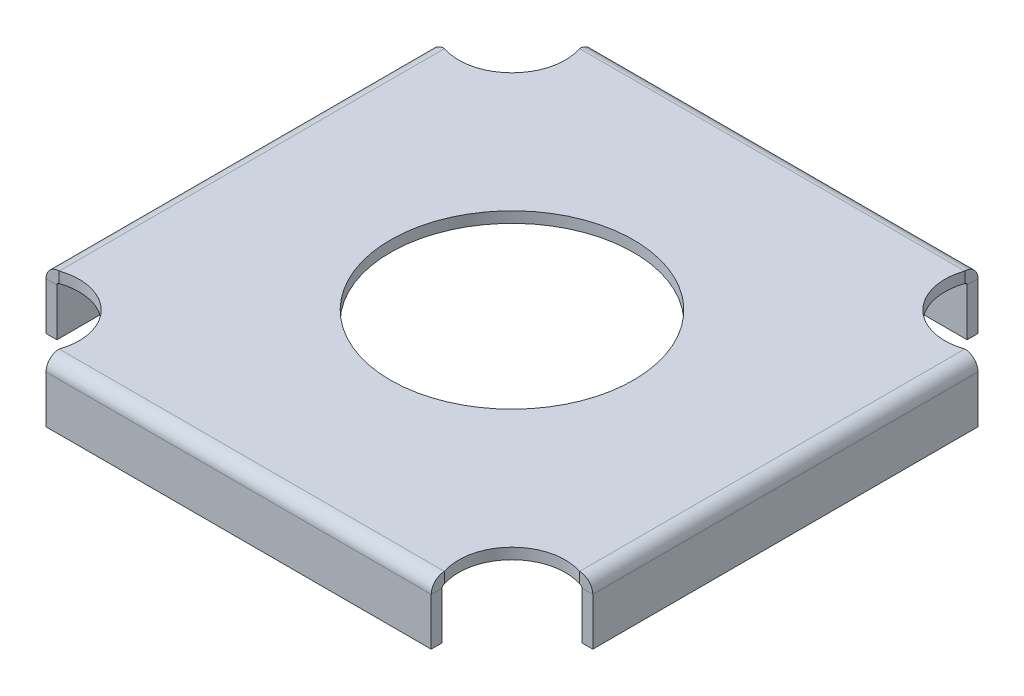
SolidWorks part; units mm, degrees
note: The reader was unsure of these and kept them because the rebuilt part matched: flange length of "Edge-Flange1".
material "Plain Carbon Steel"
ref_plane "Front Plane" through (0, 0, 0) normal (0, 0, 1) x (1, 0, 0)
ref_plane "Top Plane" through (0, 0, 0) normal (0, 1, 0) x (1, 0, 0)
ref_plane "Right Plane" through (0, 0, 0) normal (1, 0, 0) x (0, 0, -1)
sketch "Sketch3" plane through (0, 0, 0) normal (0, 1, 0) x (1, 0, 0)
  line L0 (-60.3828, 81.5594) -> (60.3828, 81.5594)
  line L5 (81.5594, 60.3828) -> (81.5594, -60.3828)
  line L6 (60.3828, -81.5594) -> (-60.3828, -81.5594)
  line L7 (-81.5594, -60.3828) -> (-81.5594, 60.3828)
  line L8 (0, 81.5594) -> (0, -81.5594) construction
  line L9 (-81.5594, 0) -> (81.5594, 0) construction
  line L10 (-76.2, 76.2) -> (-76.2, -76.2) construction
  line L11 (-76.2, -76.2) -> (76.2, -76.2) construction
  line L12 (76.2, -76.2) -> (76.2, 76.2) construction
  line L13 (76.2, 76.2) -> (-76.2, 76.2) construction
  line L14 (-76.2, 76.2) -> (76.2, -76.2) construction
  line L15 (-76.2, -76.2) -> (76.2, 76.2) construction
  arc A0 (60.3828, 81.5594) -> (81.5594, 60.3828) centre (76.2, 76.2) ccw
  arc A1 (-81.5594, 60.3828) -> (-60.3828, 81.5594) centre (-76.2, 76.2) ccw
  arc A2 (-60.3828, -81.5594) -> (-81.5594, -60.3828) centre (-76.2, -76.2) ccw
  arc A3 (81.5594, -60.3828) -> (60.3828, -81.5594) centre (76.2, -76.2) ccw
  circle A4 centre (0, 0) radius 38.1
  dimension "D2" = 163.1188
  dimension "D3" = 152.4
  dimension "D1" = 16.7005
  dimension "D4" = 76.2
base flange "Base-Flange1" sketch "Sketch3" thickness 3.4163 reverse thickness direction no parameters "D1"=0.7366
edge flange "Edge-Flange1" sketch "Sketch16" flange profiles "Sketch16", "Sketch17", "Sketch18", "Sketch19" flange angle 90 flange length 19.05 flange position bend outside bend radius 0.7366 thickness 3.4163 parameters "D6"=10, "D8"=0.254
sketch "Sketch16" plane through (0, -3.4163, 81.5594) normal (0, 0, -1) x (1, 0, 0)
  line L2 (-60.3828, 0) -> (-60.3828, 15.6337)
  line L3 (-60.3828, 15.6337) -> (60.3828, 15.6337)
  line L4 (60.3828, 15.6337) -> (60.3828, 0)
  line L9 (60.3828, 0) -> (-60.3828, 0) construction
  line L10 (60.3828, 0) -> (-60.3828, 0)
sketch "Sketch17" plane through (81.5594, -3.4163, 0) normal (-1, 0, 0) x (0, 0, -1)
  line L0 (60.3828, 0) -> (-60.3828, 0) construction
  line L1 (60.3828, 0) -> (-60.3828, 0)
  line L2 (60.3828, 0) -> (60.3828, 15.6337)
  line L3 (60.3828, 15.6337) -> (-60.3828, 15.6337)
  line L4 (-60.3828, 15.6337) -> (-60.3828, 0)
sketch "Sketch18" plane through (0, -3.4163, -81.5594) normal (0, 0, 1) x (-1, 0, 0)
  line L0 (60.3828, 0) -> (-60.3828, 0) construction
  line L1 (60.3828, 0) -> (-60.3828, 0)
  line L2 (60.3828, 0) -> (60.3828, 15.6337)
  line L3 (60.3828, 15.6337) -> (-60.3828, 15.6337)
  line L4 (-60.3828, 15.6337) -> (-60.3828, 0)
sketch "Sketch19" plane through (-81.5594, -3.4163, 0) normal (1, 0, 0) x (0, 0, 1)
  line L0 (60.3828, 0) -> (-60.3828, 0) construction
  line L1 (60.3828, 0) -> (-60.3828, 0)
  line L2 (60.3828, 0) -> (60.3828, 15.6337)
  line L3 (60.3828, 15.6337) -> (-60.3828, 15.6337)
  line L4 (-60.3828, 15.6337) -> (-60.3828, 0)
bend "EdgeBend1" bend radius 0.7366 bend angle 90 parameters "D5"=1
bend "EdgeBend2" bend radius 0.7366 bend angle 90 parameters "D5"=2
bend "EdgeBend3" bend radius 0.7366 bend angle 90 parameters "D5"=3
bend "EdgeBend4" bend radius 0.7366 bend angle 90 parameters "D5"=4
sketch "Bend-Lines1" [suppressed] plane through (0, 0, 0) normal (0, 1, 0) x (1, 0, 0)
sketch "Bounding-Box1" [suppressed] plane through (0, 0, 0) normal (0, 1, 0) x (1, 0, 0)
sketch "Sketch21" [suppressed] plane through (0, 0, 0) normal (0, 1, 0) x (1, 0, 0)
  line L0 (-83.4795, 54.5408) -> (-83.4795, 46.1588)
  line L1 (-83.4795, 60.3828) -> (-83.4795, -60.3828) construction
  line L2 (-100.2967, 60.3828) -> (-81.5594, 60.3828) construction
  line L3 (-83.4795, 37.7575) -> (-83.4795, 29.3755)
  line L4 (-83.4795, 20.9743) -> (-83.4795, 12.5923)
  line L5 (-83.4795, 4.191) -> (-83.4795, -4.191)
  line L6 (-83.4795, -12.5923) -> (-83.4795, -20.9743)
  line L7 (-83.4795, -29.3755) -> (-83.4795, -37.7575)
  line L8 (-83.4795, -46.1588) -> (-83.4795, -54.5408)
  line L9 (-81.5594, -60.3828) -> (-100.2967, -60.3828) construction
  line L10 (54.5408, 83.4795) -> (46.1588, 83.4795)
  line L11 (37.7575, 83.4795) -> (29.3755, 83.4795)
  line L12 (-46.1588, 83.4795) -> (-54.5408, 83.4795)
  line L13 (-29.3755, 83.4795) -> (-37.7575, 83.4795)
  line L14 (-12.5923, 83.4795) -> (-20.9743, 83.4795)
  line L15 (4.191, 83.4795) -> (-4.191, 83.4795)
  line L16 (20.9743, 83.4795) -> (12.5923, 83.4795)
  line L17 (83.4795, -54.5408) -> (83.4795, -46.1588)
  line L18 (83.4795, -37.7575) -> (83.4795, -29.3755)
  line L19 (83.4795, 46.1588) -> (83.4795, 54.5408)
  line L20 (83.4795, 29.3755) -> (83.4795, 37.7575)
  line L21 (83.4795, 12.5923) -> (83.4795, 20.9743)
  line L22 (83.4795, -4.191) -> (83.4795, 4.191)
  line L23 (83.4795, -20.9743) -> (83.4795, -12.5923)
  line L24 (-54.5408, -83.4795) -> (-46.1588, -83.4795)
  line L25 (-37.7575, -83.4795) -> (-29.3755, -83.4795)
  line L26 (46.1588, -83.4795) -> (54.5408, -83.4795)
  line L27 (29.3755, -83.4795) -> (37.7575, -83.4795)
  line L28 (12.5923, -83.4795) -> (20.9743, -83.4795)
  line L29 (-4.191, -83.4795) -> (4.191, -83.4795)
  line L30 (-20.9743, -83.4795) -> (-12.5923, -83.4795)
  line L31 (60.3828, 83.4795) -> (-60.3828, 83.4795) construction
  line L32 (83.4795, -60.3828) -> (83.4795, 60.3828) construction
  point P65 (0, 0)
  dimension "D1" = 5.842
  dimension "D2" = 8.382
  dimension "D4" = 5.842
  dimension "D3" = 7
  dimension "D5" = 4
extrude "Cut-Extrude-Thin1" [suppressed] cut sketch "Sketch21" against normal through all thin
sheet metal parameters "Sheet-Metal1" thickness 3.4163 parameters "D1"=0.7366
flat pattern "Flat-Pattern1" [suppressed]
sketch "Bend-Lines2" plane through (0, 0, 0) normal (0, 1, 0) x (1, 0, 0)
sketch3d "Bounding-Box2" [suppressed]
  line L0 (2.1844, -2.1844, 0) -> (-154.5844, -2.1844, 0) construction
  line L1 (2.1844, 154.5844, 0) -> (-154.5844, 154.5844, 0) construction
  line L2 (2.1844, -2.1844, 0) -> (2.1844, 154.5844, 0) construction
  line L3 (-154.5844, -2.1844, 0) -> (-154.5844, 154.5844, 0) construction
sheet metal parameters "Sheet-Metal2" thickness 3.4163 parameters "D1"=0.7366
flat pattern "Flat-Pattern1"
sketch "Bend-Lines2" plane through (0, 0, 0) normal (0, 1, 0) x (1, 0, 0)
  line L0 (-83.4795, 60.3828) -> (-83.4795, -60.3828) construction
  line L1 (60.3828, 83.4795) -> (-60.3828, 83.4795) construction
  line L2 (83.4795, -60.3828) -> (83.4795, 60.3828) construction
  line L3 (-60.3828, -83.4795) -> (60.3828, -83.4795) construction
  line L4 (-83.4795, 60.3828) -> (-83.4795, -60.3828) construction
  line L5 (60.3828, 83.4795) -> (-60.3828, 83.4795) construction
  line L6 (83.4795, -60.3828) -> (83.4795, 60.3828) construction
  line L7 (-60.3828, -83.4795) -> (60.3828, -83.4795) construction
sketch3d "Bounding-Box2" [suppressed]
  line L0 (-176.4967, 176.4967, 0) -> (-176.4967, -24.0967, 0) construction
  line L1 (24.0967, 176.4967, 0) -> (24.0967, -24.0967, 0) construction
  line L2 (-176.4967, 176.4967, 0) -> (24.0967, 176.4967, 0) construction
  line L3 (-176.4967, -24.0967, 0) -> (24.0967, -24.0967, 0) construction
bend of the flat pattern "Flatten-<EdgeBend1>1"
bend of the flat pattern "Flatten-<EdgeBend2>1"
bend of the flat pattern "Flatten-<EdgeBend3>1"
bend of the flat pattern "Flatten-<EdgeBend4>1"
